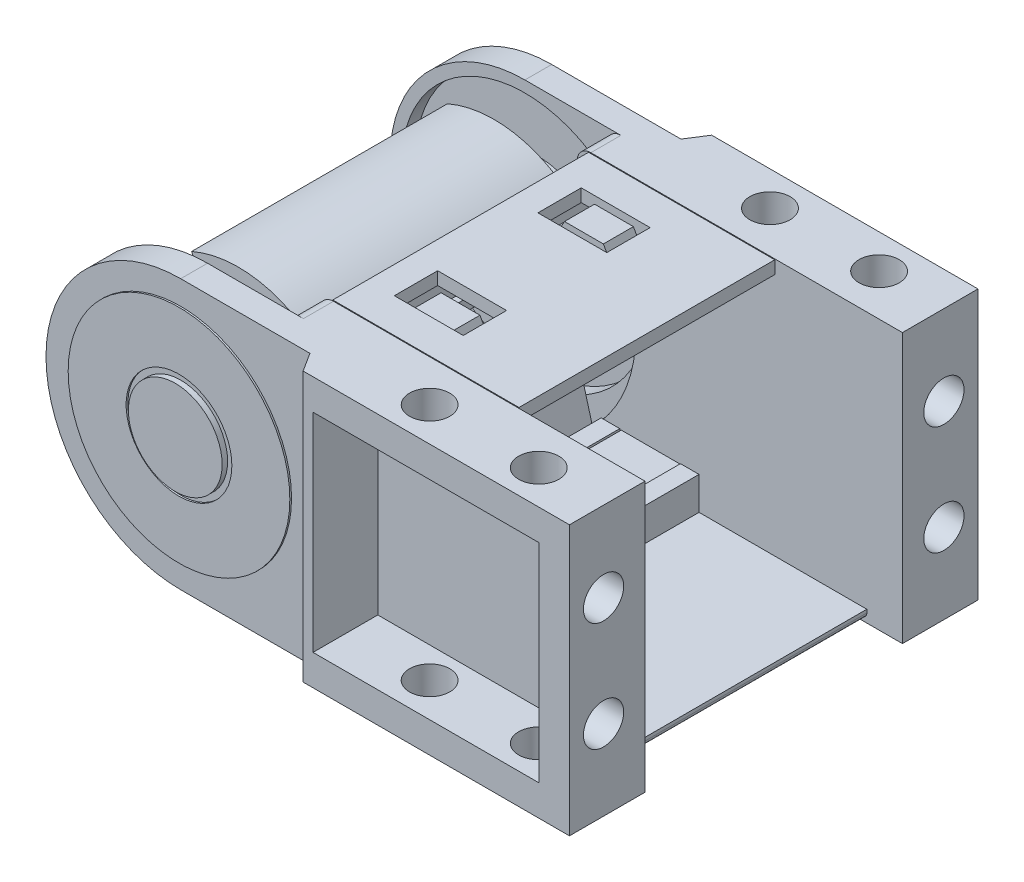
SolidWorks part; units mm, degrees
material "ABS"
ref_plane "Front Plane" through (0, 0, 0) normal (0, 0, 1) x (1, 0, 0)
ref_plane "Top Plane" through (0, 0, 0) normal (0, 1, 0) x (1, 0, 0)
ref_plane "Right Plane" through (0, 0, 0) normal (1, 0, 0) x (0, 0, -1)
sketch "Sketch1" plane through (0, 0, 0) normal (0, 0, 1) x (1, 0, 0)
  line L0 (0, 19.75) -> (59.75, 19.75)
  line L1 (59.75, 19.75) -> (59.75, -19.75)
  line L2 (59.75, -19.75) -> (0, -19.75)
  arc A0 (0, 19.75) -> (0, -19.75) centre (0, 0) ccw
  point P1 (-19.75, 0)
  dimension "D1" = 39.5
  dimension "D2" = 79.5
extrude "Boss-Extrude1" add sketch "Sketch1" against normal blind 11.08 from offset 29.95
sketch "Sketch2" plane through (0, 0, 29.95) normal (0, 0, 1) x (1, 0, 0)
  line L0 (59.75, -19.75) -> (59.75, 19.75) construction
  line L1 (22.15, 15.25) -> (55.25, 15.25)
  line L2 (22.15, 15.25) -> (22.15, -15.25)
  line L3 (22.15, -15.25) -> (55.25, -15.25)
  line L4 (55.25, 15.25) -> (55.25, -15.25)
  line L5 (38.7, -15.25) -> (38.7, 15.25) construction
  line L6 (22.15, 0) -> (55.25, 0) construction
  line L7 (59.75, 19.75) -> (0, 19.75) construction
  point P0 (38.7, 0)
  dimension "D1" = 4.5
  dimension "D2" = 4.5
  dimension "D3" = 33.1
extrude "Cut-Extrude1" cut sketch "Sketch2" against normal blind 9.5
sketch "Sketch3" plane through (0, 0, 29.95) normal (0, 0, 1) x (1, 0, 0)
  line L0 (0, -19.75) -> (59.75, -19.75) construction
  line L1 (59.75, 19.75) -> (0, 19.75) construction
  line L2 (0, -19.75) -> (18.95, -19.75)
  line L3 (18.95, 19.75) -> (0, 19.75)
  line L4 (18.95, 19.75) -> (18.95, -19.75)
  line L5 (59.75, -19.75) -> (59.75, 19.75) construction
  arc A0 (0, 19.75) -> (0, -19.75) centre (0, 0) ccw construction
  arc A1 (0, 19.75) -> (0, -19.75) centre (0, 0) ccw
  point P7 (-19.75, 0)
  dimension "D1" = 40.8
extrude "Cut-Extrude2" cut sketch "Sketch3" against normal blind 2.75
chamfer "Chamfer1" distance 1.75 distance2 2.75 1 edges at (18.95, 0, 29.95) first distance on face at (39.35, 0, 29.95)
sketch "Sketch5" plane through (0, 0, 27.2) normal (0, 0, 1) x (1, 0, 0)
  circle A0 centre (0, 0) radius 7.75
  circle A1 centre (0, 0) radius 16.25
  circle A2 centre (0, 0) radius 5.15
  dimension "D1" = 10.3
  dimension "D2" = 15.5
  dimension "D3" = 32.5
extrude "Boss-Extrude2" add sketch "Sketch5" along normal blind 0.25 contours A1 A0 region at (-15.7904, 0, 27.2)
extrude "Cut-Extrude3" cut sketch "Sketch5<3>" against normal through all contours A2 region at (0, 0, 27.2)
sketch "Sketch5<3>" plane through (0, 0, 27.2) normal (0, 0, 1) x (1, 0, 0) same geometry as "Sketch5"
sketch "Sketch6" plane through (0, 19.75, 0) normal (0, 1, 0) x (1, 0, 0)
  line L0 (59.75, -24.95) -> (20.7, -24.95) construction
  line L1 (59.75, -18.87) -> (59.75, -29.95) construction
  line L3 (59.75, -29.95) -> (20.7, -29.95) construction
  circle A0 centre (50.25, -24.95) radius 2.95
  circle A1 centre (34.25, -24.95) radius 2.95
  dimension "D1" = 5.9
  dimension "D2" = 16
  dimension "D3" = 9.5
  dimension "D4" = 5
extrude "Cut-Extrude4" cut sketch "Sketch6" against normal through all
sketch "Sketch7" plane through (59.75, 0, 0) normal (1, 0, 0) x (0, 0, -1)
  line L0 (-24.95, 19.75) -> (-24.95, -19.75) construction
  line L1 (-18.87, 19.75) -> (-29.95, 19.75) construction
  line L2 (-18.87, -19.75) -> (-29.95, -19.75) construction
  line L3 (-24.95, 0) -> (-18.87, 0) construction
  line L4 (-18.87, -19.75) -> (-18.87, 19.75) construction
  line L5 (-29.95, -19.75) -> (-29.95, 19.75) construction
  circle A0 centre (-24.95, 8) radius 2.95
  circle A1 centre (-24.95, -8) radius 2.95
  dimension "D1" = 16
  dimension "D2" = 5.9
  dimension "D3" = 5
extrude "Cut-Extrude5" cut sketch "Sketch7" against normal up to next
sketch "Sketch8" plane through (0, 0, 18.87) normal (0, 0, -1) x (-1, 0, 0)
  line L0 (19.75, 0) -> (-20.65, 0) construction
  circle A0 centre (0, 0) radius 20.65
  arc A1 (0, -19.75) -> (0, 19.75) centre (0, 0) ccw construction
  point P3 (-20.65, 0)
  point P4 (19.75, 0)
  dimension "D1" = 40.4
extrude "Cut-Extrude6" cut sketch "Sketch8" against normal blind 4.4
sketch "Sketch9" plane through (0, 0, 23.27) normal (0, 0, -1) x (-1, 0, 0)
  circle A0 centre (0, 0) radius 18.1
  dimension "D1" = 36.2
extrude "Cut-Extrude7" cut sketch "Sketch9" against normal blind 6.5 from surface starting at face at (36.545, 0, 18.87)
sketch "Sketch10" plane through (0, 0, 25.37) normal (0, 0, -1) x (-1, 0, 0)
  line L0 (0, 0) -> (16.75, 0) construction
  line L1 (8.5625, 2.5) -> (16.75, 3.2)
  line L2 (16.75, 3.2) -> (16.75, -3.2)
  line L3 (16.75, -3.2) -> (8.5625, -2.5)
  line L4 (8.8724, 0.9207) -> (15.15, 1.4574)
  line L5 (15.15, 1.4574) -> (15.15, -1.4574)
  line L6 (15.15, -1.4574) -> (8.8724, -0.9207)
  line L7 (8.6988, 0.9058) -> (15.15, 1.4574) construction
  line L8 (15.15, -1.4574) -> (8.6988, -0.9058) construction
  line L9 (0, 0) -> (0, -8.92) construction
  line L10 (-8.8724, 0.9207) -> (-15.15, 1.4574)
  line L11 (-15.15, 1.4574) -> (-15.15, -1.4574)
  line L12 (-15.15, -1.4574) -> (-8.8724, -0.9207)
  line L13 (-16.75, -3.2) -> (-8.5625, -2.5)
  line L14 (-16.75, 3.2) -> (-16.75, -3.2)
  line L15 (-8.5625, 2.5) -> (-16.75, 3.2)
  circle A0 centre (0, 0) radius 7
  arc A1 (-8.8724, 0.9207) -> (-8.8724, -0.9207) centre (0, 0) ccw
  arc A2 (-8.5625, -2.5) -> (8.5625, -2.5) centre (0, 0) ccw
  arc A3 (8.5625, 2.5) -> (-8.5625, 2.5) centre (0, 0) ccw
  arc A4 (8.8724, -0.9207) -> (8.8724, 0.9207) centre (0, 0) ccw
  point P7 (16.75, 0)
  dimension "D1" = 14
  dimension "D2" = 17.84
  dimension "D3" = 5
  dimension "D4" = 6.4
  dimension "D5" = 16.75
  dimension "D6" = 1.6
extrude "Boss-Extrude3" add sketch "Sketch10" along normal blind 3.9
fillet "Fillet1" radius 0.5 4 edges at (-16.75, -3.2, 23.42) (-16.75, 3.2, 23.42) (16.75, -3.2, 23.42) (16.75, 3.2, 23.42)
sketch "Sketch11" plane through (0, 0, 21.47) normal (0, 0, -1) x (-1, 0, 0)
  circle A0 centre (0, 0) radius 7 construction
  circle A1 centre (0, 0) radius 7
extrude "Cut-Extrude8" cut sketch "Sketch11" against normal blind 4.6
fillet "Fillet2" radius 2 2 edges at (6.0299, 19.75, 21.07) (6.0299, -19.75, 21.07)
sketch "Sketch12" plane through (0, 0, 18.87) normal (0, 0, -1) x (-1, 0, 0)
  line L0 (-27.425, 17.15) -> (-18.325, 17.15)
  line L1 (-22.875, 17.15) -> (-22.875, 13.25) construction
  line L2 (-27.425, 17.15) -> (-28.25, 15.65)
  line L3 (-28.25, 14.85) -> (-27.225, 14.85)
  line L4 (-27.225, 14.85) -> (-27.225, 13.25)
  line L5 (-18.525, 14.85) -> (-18.525, 13.25)
  line L6 (-17.5, 14.85) -> (-18.525, 14.85)
  line L7 (-18.325, 17.15) -> (-17.5, 15.65)
  line L8 (-18.525, 13.25) -> (-27.225, 13.25)
  line L9 (-28.25, 15.65) -> (-28.25, 14.85)
  line L10 (0, 0) -> (-59.75, 0) construction
  line L11 (-59.75, -19.75) -> (-59.75, 19.75) construction
  line L20 (-17.5, 15.65) -> (-17.5, 14.85)
  line L21 (-22.875, -17.15) -> (-22.875, -13.25) construction
  line L22 (-17.5, -15.65) -> (-17.5, -14.85)
  line L23 (-28.25, -15.65) -> (-28.25, -14.85)
  line L24 (-18.525, -13.25) -> (-27.225, -13.25)
  line L25 (-18.325, -17.15) -> (-17.5, -15.65)
  line L26 (-17.5, -14.85) -> (-18.525, -14.85)
  line L27 (-18.525, -14.85) -> (-18.525, -13.25)
  line L28 (-27.225, -14.85) -> (-27.225, -13.25)
  line L29 (-28.25, -14.85) -> (-27.225, -14.85)
  line L30 (-27.425, -17.15) -> (-28.25, -15.65)
  line L31 (-27.425, -17.15) -> (-18.325, -17.15)
  point P3 (-22.875, 17.15)
  dimension "D1" = 10.75
  dimension "D2" = 31.5
  dimension "D3" = 26.5
  dimension "D4" = 34.3
  dimension "D5" = 8.7
  dimension "D6" = 2.3
  dimension "D7" = 0.8
  dimension "D8" = 9.1
extrude "Boss-Extrude4" add sketch "Sketch12" along normal offset from surface (10.92 mm away) 22 up to face at (40.225, 0, 29.95)
sketch "Sketch13" plane through (0, 0, 7.95) normal (0, 0, -1) x (-1, 0, 0)
  line L0 (-26.7, 17.15) -> (-25.725, 18.9)
  line L1 (-18.325, 17.15) -> (-27.425, 17.15) construction
  line L2 (-25.725, 18.9) -> (-20.025, 18.9)
  line L3 (-20.025, 18.9) -> (-19.05, 17.15)
  line L4 (-26.7, 17.15) -> (-19.05, 17.15)
  line L5 (-22.875, 18.9) -> (-22.875, 17.15) construction
  line L6 (0, 0) -> (-59.75, 0) construction
  line L7 (-59.75, -19.75) -> (-59.75, 19.75) construction
  line L8 (-20.025, -18.9) -> (-19.05, -17.15)
  line L9 (-26.7, -17.15) -> (-19.05, -17.15)
  line L10 (-26.7, -17.15) -> (-25.725, -18.9)
  line L11 (-25.725, -18.9) -> (-20.025, -18.9)
  point P8 (-22.875, 17.15)
  dimension "D1" = 7.65
  dimension "D2" = 5.7
  dimension "D3" = 1.75
extrude "Boss-Extrude5" add sketch "Sketch13" against normal blind 4.4 from offset 1.1 offset against normal yes
sketch "Sketch14" plane through (0, 0, 0) normal (0, 0, 1) x (1, 0, 0)
  line L0 (41.15, 19.75) -> (13.85, 19.75)
  line L1 (59.75, 19.75) -> (14.0698, 19.75) construction
  line L2 (13.85, 19.75) -> (11.7872, 12.25)
  line L3 (59.75, -19.75) -> (59.75, 19.75) construction
  line L4 (41.15, 17.87) -> (30.05, 17.87)
  line L5 (15.2827, 17.87) -> (12.6469, 8.2867)
  line L6 (-6.85, 15.5588) -> (-6.0925, 13.8382)
  line L7 (41.15, 19.75) -> (41.15, 17.87)
  line L8 (30.05, 13.05) -> (30.05, 17.87)
  line L9 (27.325, 13.05) -> (30.05, 13.05)
  line L10 (27.325, 13.05) -> (27.325, 14.75)
  line L11 (27.325, 14.75) -> (28.35, 14.75)
  line L12 (28.35, 14.75) -> (28.35, 17.87)
  line L13 (28.35, 17.87) -> (17.4, 17.87)
  line L14 (41.15, 17.87) -> (15.2827, 17.87) construction
  line L15 (18.425, 13.05) -> (15.7, 13.05)
  line L16 (15.7, 13.05) -> (15.7, 17.87)
  line L17 (22.875, 13.25) -> (22.875, 19.75) construction
  line L18 (18.425, 13.25) -> (18.425, 14.75)
  line L19 (17.4, 14.75) -> (17.4, 15.65)
  line L20 (18.425, 14.75) -> (17.4, 14.75)
  line L21 (18.425, 13.05) -> (18.425, 14.75)
  line L22 (17.4, 14.75) -> (17.4, 17.87)
  line L23 (18.425, 14.75) -> (17.4, 14.75)
  line L24 (18.525, 13.25) -> (27.225, 13.25) construction
  line L25 (15.7, 17.87) -> (15.2827, 17.87)
  arc A0 (11.7872, 12.25) -> (-6.85, 15.5588) centre (0, 0) ccw
  arc A1 (12.6469, 8.2867) -> (-6.0925, 13.8382) centre (0, 0) ccw
  dimension "D1" = 17
  dimension "D2" = 48
  dimension "D3" = 27.3
  dimension "D4" = 7.5
  dimension "D5" = 18.6
  dimension "D7" = 0.1
  dimension "D6" = 1.88
  dimension "D8" = 1.7
extrude "Boss-Extrude6" add sketch "Sketch14" along normal mid plane 37.5 separate body
sketch "Sketch15" plane through (0, 19.75, 0) normal (0, 1, 0) x (1, 0, 0)
  line L1 (27.925, -7.35) -> (17.825, -7.35)
  line L2 (27.925, -7.35) -> (27.925, -13.7)
  line L5 (27.925, -13.7) -> (17.825, -13.7)
  line L6 (17.825, -7.35) -> (17.825, -13.7)
  line L7 (22.875, -13.7) -> (22.875, -7.35) construction
  line L8 (27.925, -10.525) -> (17.825, -10.525) construction
  line L9 (0, 0) -> (44.1536, 0) construction
  line L10 (17.825, 7.35) -> (17.825, 13.7)
  line L11 (27.925, 13.7) -> (17.825, 13.7)
  line L12 (27.925, 7.35) -> (27.925, 13.7)
  line L13 (27.925, 7.35) -> (17.825, 7.35)
  line L14 (19.05, -9.05) -> (26.7, -13.45) construction
  point P14 (22.875, -11.25)
  point P172 (22.875, -10.525)
  dimension "D1" = 10.1
  dimension "D2" = 14.7
  dimension "D3" = 27.4
extrude "Cut-Extrude9" cut sketch "Sketch15" against normal up to surface (5 mm away) up to face at (27.8375, 14.75, 0)
sketch "Sketch16" plane through (0, 13.05, 0) normal (0, -1, 0) x (1, 0, 0)
  line L0 (30.05, 18.75) -> (30.05, -18.75) construction
  line L1 (30.05, 1) -> (15.7, 1)
  line L2 (30.05, 1) -> (30.05, -1)
  line L3 (30.05, -1) -> (15.7, -1)
  line L4 (15.7, 1) -> (15.7, -1)
  line L5 (22.875, -1) -> (22.875, 1) construction
  line L6 (30.05, 0) -> (15.7, 0) construction
  line L7 (15.7, 18.75) -> (15.7, -18.75) construction
  point P10 (22.875, 0)
  point P212 (22.875, 0)
  dimension "D1" = 2
extrude "Boss-Extrude7" add sketch "Sketch16" against normal up to surface (4.82 mm away) up to face at (35.6, 17.87, 0)
sketch "Sketch18" plane through (0, 0, 27.2) normal (0, 0, 1) x (1, 0, 0)
  circle A0 centre (0, 0) radius 6.875
  dimension "D1" = 13.75
extrude "Boss-Extrude9" add sketch "Sketch18" along normal blind 0.8 separate body
sketch "Sketch19" plane through (0, 0, 27.2) normal (0, 0, -1) x (-1, 0, 0)
  circle A2 centre (0, 0) radius 5.1
  circle A3 centre (0, 0) radius 5.1
  dimension "D1" = 0.05
extrude "Boss-Extrude10" add sketch "Sketch19" along normal blind 8
mirror "Mirror1" about plane through (0, 0, 0) normal (0, 0, 1) of bodies 113 121
mirror "Mirror2" about plane through (0, 0, 0) normal (0, 1, 0) of bodies 118 115
sketch "Sketch20" plane through (41.15, 0, 0) normal (1, 0, 0) x (0, 0, -1)
  line L4 (18.75, -19.75) -> (18.75, -17.87)
  line L5 (18.75, -17.87) -> (-18.75, -17.87)
  line L6 (-18.75, -17.87) -> (-18.75, -19.75)
  line L7 (-18.75, -19.75) -> (18.75, -19.75)
  line L8 (18.75, -19.75) -> (18.75, -17.87)
  line L9 (18.75, -17.87) -> (-18.75, -17.87)
  line L10 (-18.75, -17.87) -> (-18.75, -19.75)
  line L11 (-18.75, -19.75) -> (18.75, -19.75)
  dimension "D1" = 0
extrude "Boss-Extrude11" add sketch "Sketch20" along normal blind 13.5
chamfer "Chamfer2" distance 2 angle 25 1 edges at (54.65, -19.75, 0) first distance on face at (22.875, -19.75, 10.525)
fillet "Fillet3" radius 0.75 1 edges at (54.65, -18.8174, 0)
fillet "Fillet4" radius 10 1 edges at (52.65, -19.75, 0)
